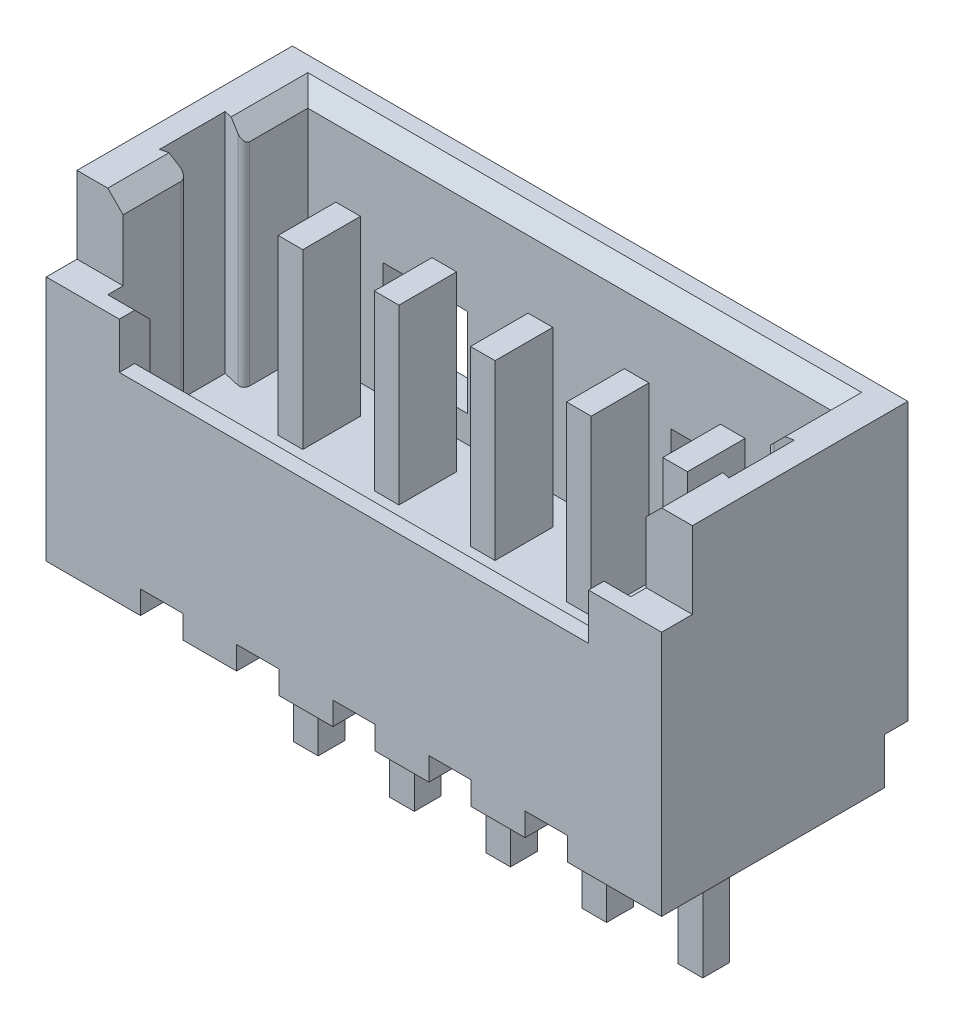
SolidWorks part; units mm, degrees
ref_plane "Front Plane" through (0, 0, 0) normal (0, 0, 1) x (1, 0, 0)
ref_plane "Top Plane" through (0, 0, 0) normal (0, 1, 0) x (1, 0, 0)
ref_plane "Right Plane" through (0, 0, 0) normal (1, 0, 0) x (0, 0, -1)
ref_plane "Plane1" through (0, 0, 1.6) normal (0, 0, 1) x (1, 0, 0)
sketch "Sketch1" plane through (0, 0, 1.6) normal (0, 0, 1) x (1, 0, 0)
  line L0 (-4, 0.975) -> (-4, -3.225)
  line L1 (-4, -3.225) -> (4, -3.225)
  line L2 (4, -3.225) -> (4, 0.975)
  line L3 (4, 0.975) -> (-4, 0.975)
extrude "Boss-Extrude1" add sketch "Sketch1" against normal blind 2.8
ref_plane "Plane2" through (3.05, 0, 0) normal (1, 0, 0) x (0, 0, -1)
sketch "Sketch2" plane through (3.05, 0, 0) normal (1, 0, 0) x (0, 0, -1)
  line L0 (1.2, 0.975) -> (-1.6, 0.975)
  line L1 (-1.6, 0.975) -> (-1.6, -0.625)
  line L2 (-1.6, -0.625) -> (-1.4, -0.625)
  line L3 (-1.4, -0.625) -> (-1.2, -0.825)
  line L4 (-1.2, -0.825) -> (-1.2, -1.975)
  line L5 (-1.2, -1.975) -> (1.2, -1.975)
  line L6 (1.2, -1.975) -> (1.2, 0.975)
extrude "Cut-Extrude1" cut sketch "Sketch2" against normal blind 6.1
sketch "Sketch3" plane through (0, 0, 1.6) normal (0, 0, 1) x (1, 0, 0)
  line L0 (4, 0.975) -> (3.05, 0.975)
  line L1 (3.05, 0.975) -> (3.05, -0.025)
  line L2 (3.05, -0.025) -> (4, -0.025)
  line L3 (4, -0.025) -> (4, 0.975)
extrude "Cut-Extrude2" cut sketch "Sketch3" against normal blind 0.4
sketch "Sketch4" plane through (0, 0.975, 0) normal (0, 1, 0) x (-1, 0, 0)
  line L0 (3.05, 1.6) -> (3.05, 1.2)
  line L1 (3.4, 1.2) -> (4, 1.2)
  line L2 (4, 1.2) -> (4, 1.6)
  line L3 (4, 1.6) -> (3.05, 1.6)
  spline S0 degree 3 poles (3.05, 1.2) (3.1667, 1.2) (3.2833, 1.2) (3.4, 1.2) knots 0 0 0 0 1 1 1 1
extrude "Cut-Extrude3" cut sketch "Sketch4" against normal blind 1
sketch "Sketch5" plane through (3.05, 0, 0) normal (-1, 0, 0) x (0, 0, 1)
  line L0 (-1.2, -1.975) -> (1.2, -1.975)
  line L1 (1.2, -1.975) -> (1.2, -0.225)
  line L2 (1.2, -0.225) -> (1.4, -0.025)
  line L3 (1.4, -0.025) -> (1.2, -0.025)
  line L4 (1.2, -0.025) -> (1.2, 0.975)
  line L5 (1.2, 0.975) -> (-1.2, 0.975)
  line L6 (-1.2, 0.975) -> (-1.2, -1.975)
extrude "Cut-Extrude4" cut sketch "Sketch5" against normal blind 0.35
sketch "Sketch6" plane through (-3.05, 0, 0) normal (1, 0, 0) x (0, 0, -1)
  line L0 (1.2, -1.975) -> (1.2, 0.975)
  line L1 (1.2, 0.975) -> (-1.2, 0.975)
  line L2 (-1.2, 0.975) -> (-1.2, -0.025)
  line L3 (-1.2, -0.025) -> (-1.4, -0.025)
  line L4 (-1.4, -0.025) -> (-1.2, -0.225)
  line L5 (-1.2, -0.225) -> (-1.2, -1.975)
  line L6 (-1.2, -1.975) -> (1.2, -1.975)
extrude "Cut-Extrude5" cut sketch "Sketch6" against normal blind 0.35
sketch "Sketch7" plane through (0, 0, -1.2) normal (0, 0, -1) x (-1, 0, 0)
  line L0 (4, -3.225) -> (-4, -3.225)
  line L1 (-4, -3.225) -> (-4, 0.975)
  line L2 (-4, 0.975) -> (4, 0.975)
  line L3 (4, 0.975) -> (4, -3.225)
extrude "Boss-Extrude2" add sketch "Sketch7" along normal blind 0.4
sketch "Sketch8" plane through (0, 0, 1.6) normal (0, 0, 1) x (1, 0, 0)
  line L0 (-1.525, -3.225) -> (-0.975, -3.225)
  line L1 (-0.975, -3.225) -> (-0.975, -3.125)
  line L2 (-0.975, -3.125) -> (-1.525, -3.125)
  line L3 (-1.525, -3.125) -> (-1.525, -3.225)
extrude "Cut-Extrude6" cut sketch "Sketch8" against normal blind 3.2
ref_plane "Plane3" through (0, -3.125, 0) normal (0, -1, 0) x (1, 0, 0)
ref_plane "Plane4" through (0, -2.925, 0) normal (0, 1, 0) x (1, 0, 0)
sketch "Sketch10" plane through (0, -2.925, 0) normal (0, 1, 0) x (1, 0, 0)
  line L0 (-1.525, -0.4) -> (-1.525, -1.6)
  line L1 (-1.525, -1.6) -> (-0.975, -1.6)
  line L2 (-0.975, -1.6) -> (-0.975, -0.4)
  line L3 (-0.975, -0.4) -> (-1.525, -0.4)
extrude "Cut-Extrude7" cut sketch "Sketch10" against normal up to surface up to plane "Plane3"
sketch "Sketch11" plane through (0, 0, 1.6) normal (0, 0, 1) x (1, 0, 0)
  line L0 (-0.275, -3.225) -> (0.275, -3.225)
  line L1 (0.275, -3.225) -> (0.275, -3.125)
  line L2 (0.275, -3.125) -> (-0.275, -3.125)
  line L3 (-0.275, -3.125) -> (-0.275, -3.225)
extrude "Cut-Extrude8" cut sketch "Sketch11" against normal blind 3.2
sketch "Sketch13" plane through (0, -2.925, 0) normal (0, 1, 0) x (1, 0, 0)
  line L0 (-0.275, -0.4) -> (-0.275, -1.6)
  line L1 (-0.275, -1.6) -> (0.275, -1.6)
  line L2 (0.275, -1.6) -> (0.275, -0.4)
  line L3 (0.275, -0.4) -> (-0.275, -0.4)
extrude "Cut-Extrude9" cut sketch "Sketch13" against normal up to surface up to plane "Plane3"
sketch "Sketch14" plane through (0, 0, 1.6) normal (0, 0, 1) x (1, 0, 0)
  line L0 (0.975, -3.225) -> (1.525, -3.225)
  line L1 (1.525, -3.225) -> (1.525, -3.125)
  line L2 (1.525, -3.125) -> (0.975, -3.125)
  line L3 (0.975, -3.125) -> (0.975, -3.225)
extrude "Cut-Extrude10" cut sketch "Sketch14" against normal blind 3.2
sketch "Sketch16" plane through (0, -2.925, 0) normal (0, 1, 0) x (1, 0, 0)
  line L0 (0.975, -0.4) -> (0.975, -1.6)
  line L1 (0.975, -1.6) -> (1.525, -1.6)
  line L2 (1.525, -1.6) -> (1.525, -0.4)
  line L3 (1.525, -0.4) -> (0.975, -0.4)
extrude "Cut-Extrude11" cut sketch "Sketch16" against normal up to surface up to plane "Plane3"
sketch "Sketch17" plane through (0, 0, 1.6) normal (0, 0, 1) x (1, 0, 0)
  line L0 (2.225, -3.225) -> (2.775, -3.225)
  line L1 (2.775, -3.225) -> (2.775, -3.125)
  line L2 (2.775, -3.125) -> (2.225, -3.125)
  line L3 (2.225, -3.125) -> (2.225, -3.225)
extrude "Cut-Extrude12" cut sketch "Sketch17" against normal blind 3.2
sketch "Sketch19" plane through (0, -2.925, 0) normal (0, 1, 0) x (1, 0, 0)
  line L0 (2.775, -0.4) -> (2.225, -0.4)
  line L1 (2.225, -0.4) -> (2.225, -1.6)
  line L2 (2.225, -1.6) -> (2.775, -1.6)
  line L3 (2.775, -1.6) -> (2.775, -0.4)
extrude "Cut-Extrude13" cut sketch "Sketch19" against normal up to surface up to plane "Plane3"
sketch "Sketch20" plane through (0, 0, 1.6) normal (0, 0, 1) x (1, 0, 0)
  line L0 (-2.775, -3.225) -> (-2.225, -3.225)
  line L1 (-2.225, -3.225) -> (-2.225, -3.125)
  line L2 (-2.225, -3.125) -> (-2.775, -3.125)
  line L3 (-2.775, -3.125) -> (-2.775, -3.225)
extrude "Cut-Extrude14" cut sketch "Sketch20" against normal blind 3.2
sketch "Sketch22" plane through (0, -2.925, 0) normal (0, 1, 0) x (1, 0, 0)
  line L0 (-2.775, -0.4) -> (-2.775, -1.6)
  line L1 (-2.775, -1.6) -> (-2.225, -1.6)
  line L2 (-2.225, -1.6) -> (-2.225, -0.4)
  line L3 (-2.225, -0.4) -> (-2.775, -0.4)
extrude "Cut-Extrude15" cut sketch "Sketch22" against normal up to surface up to plane "Plane3"
ref_plane "Plane5" through (0, -2.625, 0) normal (0, 1, 0) x (1, 0, 0)
sketch "Sketch24" plane through (0, -2.625, 0) normal (0, 1, 0) x (1, 0, 0)
  line L0 (-2.775, 1.6) -> (-2.775, 1.3)
  line L1 (-2.775, 1.3) -> (-2.225, 1.3)
  line L2 (-2.225, 1.3) -> (-2.225, 1.6)
  line L3 (-2.225, 1.6) -> (-2.775, 1.6)
extrude "Cut-Extrude16" cut sketch "Sketch24" against normal up to surface up to plane "Plane3"
sketch "Sketch26" plane through (0, -2.625, 0) normal (0, 1, 0) x (1, 0, 0)
  line L0 (2.225, 1.3) -> (2.775, 1.3)
  line L1 (2.775, 1.3) -> (2.775, 1.6)
  line L2 (2.775, 1.6) -> (2.225, 1.6)
  line L3 (2.225, 1.6) -> (2.225, 1.3)
extrude "Cut-Extrude17" cut sketch "Sketch26" against normal up to surface up to plane "Plane3"
sketch "Sketch28" plane through (0, -2.625, 0) normal (0, 1, 0) x (1, 0, 0)
  line L0 (0.975, 1.6) -> (0.975, 1.3)
  line L1 (0.975, 1.3) -> (1.525, 1.3)
  line L2 (1.525, 1.3) -> (1.525, 1.6)
  line L3 (1.525, 1.6) -> (0.975, 1.6)
extrude "Cut-Extrude18" cut sketch "Sketch28" against normal up to surface up to plane "Plane3"
sketch "Sketch30" plane through (0, -2.625, 0) normal (0, 1, 0) x (1, 0, 0)
  line L0 (-0.275, 1.6) -> (-0.275, 1.3)
  line L1 (-0.275, 1.3) -> (0.275, 1.3)
  line L2 (0.275, 1.3) -> (0.275, 1.6)
  line L3 (0.275, 1.6) -> (-0.275, 1.6)
extrude "Cut-Extrude19" cut sketch "Sketch30" against normal up to surface up to plane "Plane3"
sketch "Sketch32" plane through (0, -2.625, 0) normal (0, 1, 0) x (1, 0, 0)
  line L0 (-1.525, 1.6) -> (-1.525, 1.3)
  line L1 (-1.525, 1.3) -> (-0.975, 1.3)
  line L2 (-0.975, 1.3) -> (-0.975, 1.6)
  line L3 (-0.975, 1.6) -> (-1.525, 1.6)
extrude "Cut-Extrude20" cut sketch "Sketch32" against normal up to surface up to plane "Plane3"
sketch "Sketch33" plane through (0, 0.975, 0) normal (0, 1, 0) x (-1, 0, 0)
  line L0 (3.7, -0.3568) -> (3.7, 0.4268)
  line L1 (3.7, 0.4268) -> (3.4, 0.3568)
  line L2 (3.4, 0.3568) -> (3.4, -0.3568)
  line L3 (3.4, -0.3568) -> (3.7, -0.3568)
extrude "Cut-Extrude21" cut sketch "Sketch33" against normal blind 2.95
sketch "Sketch34" plane through (0, 0.975, 0) normal (0, 1, 0) x (-1, 0, 0)
  line L0 (-3.4, -0.4268) -> (-3.4, 0.4268)
  line L1 (-3.4, 0.4268) -> (-3.7, 0.4268)
  line L2 (-3.7, 0.4268) -> (-3.7, -0.4268)
  line L3 (-3.7, -0.4268) -> (-3.4, -0.4268)
extrude "Cut-Extrude22" cut sketch "Sketch34" against normal blind 2.95
sketch "Sketch35" plane through (0, 0, -1.2) normal (0, 0, 1) x (1, 0, 0)
  line L0 (-2.425, -1.625) -> (-1.325, -1.625)
  line L1 (-1.325, -1.625) -> (-1.325, -0.475)
  line L2 (-1.325, -0.475) -> (-2.425, -0.475)
  line L3 (-2.425, -0.475) -> (-2.425, -1.625)
extrude "Cut-Extrude23" cut sketch "Sketch35" against normal through all
sketch "Sketch36" plane through (0, 0, -1.6) normal (0, 0, -1) x (-1, 0, 0)
  line L0 (-1.325, -1.625) -> (-1.325, -0.475)
  line L1 (-1.325, -0.475) -> (-2.425, -0.475)
  line L2 (-2.425, -0.475) -> (-2.425, -1.625)
  line L3 (-2.425, -1.625) -> (-1.325, -1.625)
extrude "Cut-Extrude24" cut sketch "Sketch36" against normal up to next
sketch "Sketch37" plane through (0, -3.225, 0) normal (0, -1, 0) x (1, 0, 0)
  line L0 (-3.425, -1.3) -> (-4, -1.3)
  line L1 (-4, -1.3) -> (-4, -1.6)
  line L2 (-4, -1.6) -> (-3.425, -1.6)
  line L3 (-3.425, -1.6) -> (-3.425, -1.3)
extrude "Cut-Extrude25" cut sketch "Sketch37" against normal blind 0.6
sketch "Sketch38" plane through (4, 0, 0) normal (1, 0, 0) x (0, 0, -1)
  line L0 (1.3, -2.625) -> (1.3, -3.225)
  line L1 (1.3, -3.225) -> (1.6, -3.225)
  line L2 (1.6, -3.225) -> (1.6, -2.625)
  line L3 (1.6, -2.625) -> (1.3, -2.625)
extrude "Cut-Extrude26" cut sketch "Sketch38" against normal blind 0.575
sketch "Sketch39" plane through (0, -3.125, 0) normal (0, -1, 0) x (1, 0, 0)
  line L0 (1.41, -0.275) -> (1.41, -0.625)
  line L1 (1.41, -0.625) -> (1.09, -0.625)
  line L2 (1.09, -0.625) -> (1.09, -0.275)
  line L3 (1.09, -0.275) -> (1.41, -0.275)
extrude "Boss-Extrude3" add sketch "Sketch39" along normal blind 2.4
sketch "Sketch40" plane through (0, -3.125, 0) normal (0, -1, 0) x (1, 0, 0)
  line L0 (0.16, -0.275) -> (0.16, -0.625)
  line L1 (0.16, -0.625) -> (-0.16, -0.625)
  line L2 (-0.16, -0.625) -> (-0.16, -0.275)
  line L3 (-0.16, -0.275) -> (0.16, -0.275)
extrude "Boss-Extrude4" add sketch "Sketch40" along normal blind 2.4
sketch "Sketch41" plane through (0, -3.125, 0) normal (0, -1, 0) x (1, 0, 0)
  line L0 (-1.09, -0.275) -> (-1.09, -0.625)
  line L1 (-1.09, -0.625) -> (-1.41, -0.625)
  line L2 (-1.41, -0.625) -> (-1.41, -0.275)
  line L3 (-1.41, -0.275) -> (-1.09, -0.275)
extrude "Boss-Extrude5" add sketch "Sketch41" along normal blind 2.4
sketch "Sketch42" plane through (0, -3.125, 0) normal (0, -1, 0) x (1, 0, 0)
  line L0 (-2.34, -0.275) -> (-2.34, -0.625)
  line L1 (-2.34, -0.625) -> (-2.66, -0.625)
  line L2 (-2.66, -0.625) -> (-2.66, -0.275)
  line L3 (-2.66, -0.275) -> (-2.34, -0.275)
extrude "Boss-Extrude6" add sketch "Sketch42" along normal blind 2.4
sketch "Sketch43" plane through (0, -3.125, 0) normal (0, -1, 0) x (1, 0, 0)
  line L0 (2.66, -0.275) -> (2.66, -0.625)
  line L1 (2.66, -0.625) -> (2.34, -0.625)
  line L2 (2.34, -0.625) -> (2.34, -0.275)
  line L3 (2.34, -0.275) -> (2.66, -0.275)
extrude "Boss-Extrude7" add sketch "Sketch43" along normal blind 2.4
sketch "Sketch44" plane through (0, -1.975, 0) normal (0, 1, 0) x (-1, 0, 0)
  line L0 (-2.34, -0.825) -> (-2.66, -0.825)
  line L1 (-2.66, -0.825) -> (-2.66, -0.075)
  line L2 (-2.66, -0.075) -> (-2.34, -0.075)
  line L3 (-2.34, -0.075) -> (-2.34, -0.825)
extrude "Boss-Extrude8" add sketch "Sketch44" along normal blind 2.25
sketch "Sketch45" plane through (0, -1.975, 0) normal (0, 1, 0) x (-1, 0, 0)
  line L0 (-1.09, -0.825) -> (-1.41, -0.825)
  line L1 (-1.41, -0.825) -> (-1.41, -0.075)
  line L2 (-1.41, -0.075) -> (-1.09, -0.075)
  line L3 (-1.09, -0.075) -> (-1.09, -0.825)
extrude "Boss-Extrude9" add sketch "Sketch45" along normal blind 2.25
sketch "Sketch46" plane through (0, -1.975, 0) normal (0, 1, 0) x (-1, 0, 0)
  line L0 (0.16, -0.825) -> (-0.16, -0.825)
  line L1 (-0.16, -0.825) -> (-0.16, -0.075)
  line L2 (-0.16, -0.075) -> (0.16, -0.075)
  line L3 (0.16, -0.075) -> (0.16, -0.825)
extrude "Boss-Extrude10" add sketch "Sketch46" along normal blind 2.25
sketch "Sketch47" plane through (0, -1.975, 0) normal (0, 1, 0) x (-1, 0, 0)
  line L0 (1.41, -0.825) -> (1.09, -0.825)
  line L1 (1.09, -0.825) -> (1.09, -0.075)
  line L2 (1.09, -0.075) -> (1.41, -0.075)
  line L3 (1.41, -0.075) -> (1.41, -0.825)
extrude "Boss-Extrude11" add sketch "Sketch47" along normal blind 2.25
sketch "Sketch48" plane through (0, -1.975, 0) normal (0, 1, 0) x (-1, 0, 0)
  line L0 (2.66, -0.825) -> (2.34, -0.825)
  line L1 (2.34, -0.825) -> (2.34, -0.075)
  line L2 (2.34, -0.075) -> (2.66, -0.075)
  line L3 (2.66, -0.075) -> (2.66, -0.825)
extrude "Boss-Extrude12" add sketch "Sketch48" along normal blind 2.25
draft "Draft1" type of draft neutral plane draft angle 13.146 faces to draft 1 face at (-3.55, -0.5, -0.3568) neutral plane through (-3.4, 0, 0) neutral plane normal (1, 0, 0) reverse direction yes parameters "D1"=13.146
draft "Draft2" type of draft neutral plane draft angle 13.146 faces to draft 2 face at (3.55, -0.5, -0.4268) face at (3.55, -0.5, 0.4268) neutral plane through (3.7, -1.975, 0.4268) neutral plane normal (-1, 0, 0) reverse direction yes parameters "D1"=13.146
fillet "Fillet1" radius 0.07 4 edges at (3.4, -0.5, -0.3568) (-3.4, -0.5, 0.3568) (3.4, -0.5, 0.3568) (-3.4, -0.5, -0.3568) tangent propagation no
chamfer "Chamfer1" distance 0.2 angle 45 5 edges at (3.4, 0.975, 0.8225) (-3.4, 0.975, 0.8225) (3.4, 0.975, -0.8225) (0, 0.975, -1.2) (-3.4, 0.975, -0.8225)
